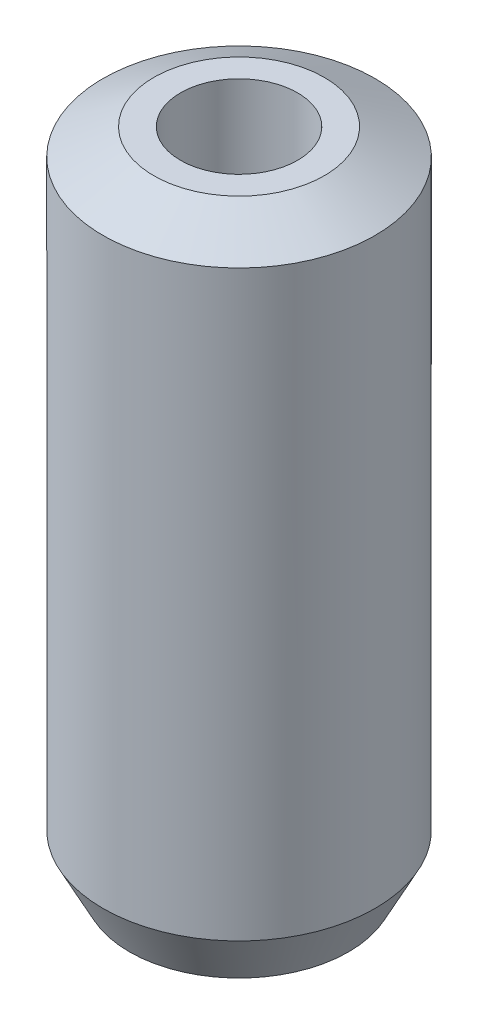
SolidWorks part; units mm, degrees
ref_plane "Front Plane" through (0, 0, 0) normal (0, 0, 1) x (1, 0, 0)
ref_plane "Top Plane" through (0, 0, 0) normal (0, 1, 0) x (1, 0, 0)
ref_plane "Right Plane" through (0, 0, 0) normal (1, 0, 0) x (0, 0, -1)
sketch "Sketch1" plane through (0, 0, 0) normal (0, 1, 0) x (1, 0, 0)
  circle A0 centre (0, 0) radius 15
  dimension "SHAFT_OD" = 30
extrude "Boss-Extrude1" add sketch "Sketch1" along normal blind 72.7822
sketch "Sketch2" plane through (0, 0, 0) normal (0, 1, 0) x (1, 0, 0)
  circle A0 centre (0, 0) radius 6.4559
  dimension "BORE_D" = 12.9118
extrude "Cut-Extrude1" cut sketch "Sketch2" along normal through all
chamfer "Chamfer1" distance 2.9051 angle 62.575 2 edges at (0, 72.7822, 15) (0, 0, 15) first distance on face at (0, 72.7822, 15) first distance on face at (0, 0, 6.4559)
